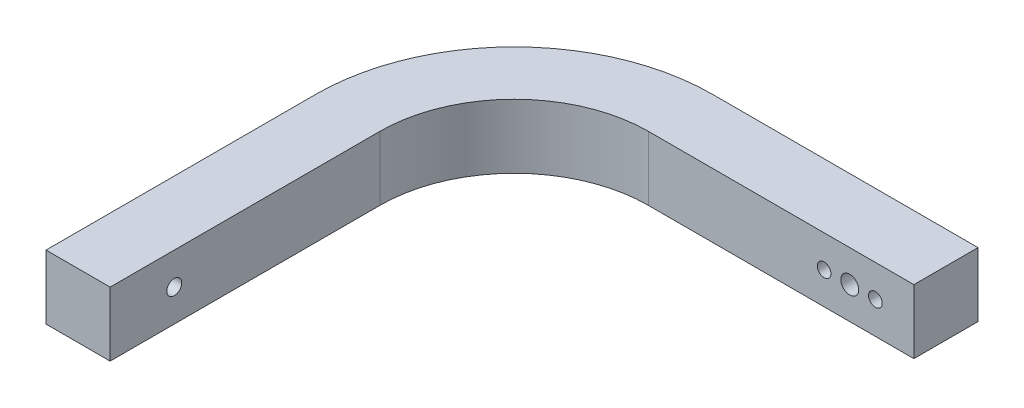
SolidWorks part; units mm, degrees
ref_plane "Front Plane" through (0, 0, 0) normal (0, 0, 1) x (1, 0, 0)
ref_plane "Top Plane" through (0, 0, 0) normal (0, 1, 0) x (1, 0, 0)
ref_plane "Right Plane" through (0, 0, 0) normal (1, 0, 0) x (0, 0, -1)
ref_axis "Z" through (0, 0, -5.375) along (0, 0, 1)
sketch "Sketch1" plane through (0, 0, 0) normal (0, 1, 0) x (1, 0, 0)
  line L0 (-47.1, 0) -> (47.1, 0) construction
  line L1 (-93.5, -46.4) -> (-93.5, -109.5)
  line L2 (-93.5, -109.5) -> (-78.5, -109.5)
  line L3 (-78.5, -109.5) -> (-78.5, -46.4)
  line L4 (-47.1, -15) -> (47.1, -15) construction
  line L5 (0, -15) -> (0, 0) construction
  line L6 (78.5, -109.5) -> (78.5, -46.4) construction
  line L7 (93.5, -109.5) -> (78.5, -109.5) construction
  line L8 (93.5, -46.4) -> (93.5, -109.5) construction
  line L9 (47.1, 0) -> (47.1, -15) construction
  line L10 (15, -15) -> (15, 0)
  line L11 (-47.1, -15) -> (15, -15)
  line L12 (-47.1, 0) -> (15, 0)
  line L13 (0, 5.375) -> (0, -112.875) construction
  arc A0 (-47.1, 0) -> (-93.5, -46.4) centre (-47.1, -46.4) ccw
  arc A1 (-78.5, -46.4) -> (-47.1, -15) centre (-47.1, -46.4) cw
  arc A2 (78.5, -46.4) -> (47.1, -15) centre (47.1, -46.4) ccw construction
  arc A3 (47.1, 0) -> (93.5, -46.4) centre (47.1, -46.4) cw construction
  point P10 (22.0594, -22.0981)
  dimension "D3" = 31.4
  dimension "D1" = 157
  dimension "D2" = 15
  dimension "D4" = 94.5
  dimension "D5" = 15
extrude "Boss-Extrude1" add sketch "Sketch1" along normal blind 7.5 and the other way blind 7.5
sketch "Sketch2" plane through (-78.5, 0, 0) normal (-1, 0, 0) x (0, 0, 1)
  line L1 (59.125, 0) -> (-59.125, 0) construction
  line L2 (0, -8.25) -> (0, 8.25) construction
  circle A0 centre (94.5, 0) radius 1.75
  dimension "D1" = 3.5
  dimension "D2" = 94.5
extrude "Cut-Extrude1" cut sketch "Sketch2" against normal through all both and the other way through all
ref_axis "Axis2" through (-120.1767, 0, 94.5) along (1, 0, 0)
sketch "Sketch3" plane through (0, 0, 0) normal (0, 0, -1) x (-1, 0, 0)
  line L0 (-6, 0) -> (6, 0) construction
  circle A0 centre (0, 0) radius 2.1
  circle A1 centre (-6, 0) radius 1.6
  circle A2 centre (6, 0) radius 1.6
  dimension "D1" = 4.2
  dimension "D3" = 3.2
  dimension "D2" = 12
extrude "Cut-Extrude2" cut sketch "Sketch3" against normal through all
sketch "Sketch4" plane through (-93.5, 0, 0) normal (1, 0, 0) x (0, 0, -1)
  circle A0 centre (-94.5, 0) radius 2.275
  circle A1 centre (-94.5, 0) radius 1.75 construction
  dimension "D1" = 4.55
extrude "Cut-Extrude3" cut sketch "Sketch4" along normal blind 6
sketch "Sketch5" plane through (-93.5, 0, 0) normal (-1, 0, 0) x (0, 0, 1)
  circle A0 centre (94.5, 0) radius 3.825
  dimension "D1" = 7.65
extrude "Cut-Extrude4" cut sketch "Sketch5" against normal blind 0.75
equation "\"width\"= \"EyeDiameter\" + \"EyeClearance\""
equation "\"prongwidth\"= \"L2Thickness\""
equation "\"D2@Sketch1\"=\"prongwidth\""
equation "\"D3@Sketch1\"=\"width\"/5"
equation "\"pronglength\"= \"BasePlaneDistance\"'model implicitly adds clearance (of prongwidth) to the hole drilled at the baseplanedistance"
equation "\"D4@Sketch1\"=\"pronglength\""
equation "\"D1@Boss-Extrude1\"=\"prongwidth\"/2"
equation "\"D2@Boss-Extrude1\"=\"prongwidth\"/2"
equation "\"lbracket-plane-to-axis\"= \"BasePlaneDistance\""
equation "\"D2@Sketch2\"=\"lbracket-plane-to-axis\""
equation "\"EyeDiameter\" = 155"
equation "\"BasePlaneDistance\" = \"EyeDiameter\"/2+\"L2Thickness\"+\"EyeClearance\""
equation "\"EyeClearance\" = 2"
equation "\"D1@Sketch1\"=\"EyeDiameter\"+\"EyeClearance\""
equation "\"BearingDepth\"= 6"
equation "\"BearingHousingID\"=4.5"
equation "\"D1@Sketch4\"=\"BearingHousingID\" + \"PrinterFilamentThickness\" * \"ApplyPrinterOffset\" / 2"
equation "\"D1@Cut-Extrude3\"=\"BearingDepth\""
equation "\"BearingFlangeThickness\"= 0.75"
equation "\"BearingFlangeOD\"=7.5"
equation "\"D1@Sketch5\"=\"BearingFlangeOD\" + \"PrinterFilamentThickness\"*1.5 *\"ApplyPrinterOffset\""
equation "\"D1@Cut-Extrude4\"=\"BearingFlangeThickness\""
equation "\"PrinterFilamentThickness\"= 0.1"
equation "\"ApplyPrinterOffset\"= 1'if 1, adjust hole sizes to try and make pressfits work with the 3d printer"
equation "\"L2Thickness\" = 15"
equation "\"L2_ID\" = 20"
equation "\"vx\" = 0"
equation "\"vy\" = 0"
equation "\"vz\" = 100"
equation "\"parametric_end\" = 1"
equation "\"Rw_3_xx\" = -(\"vz\")/sqr((\"vx\")^2 + (\"vz\")^2)"
equation "\"Rw_3_xy\" = 0"
equation "\"Rw_3_xz\" = (\"vx\")/sqr((\"vx\")^2 + (\"vz\")^2)"
equation "\"Rw_3_zx\" = (\"vx\")/sqr((\"vx\")^2 + (\"vy\")^2 + (\"vz\")^2)"
equation "\"Rw_3_zy\" = (\"vy\")/sqr((\"vx\")^2 + (\"vy\")^2 + (\"vz\")^2)"
equation "\"Rw_3_zz\" = (\"vz\")/sqr((\"vx\")^2 + (\"vy\")^2 + (\"vz\")^2)"
equation "\"Rw_3_yx\" = (\"vx\")*(\"vy\")/sqr((\"vx\")^4 + (\"vx\")^2*(\"vy\")^2 + 2*(\"vx\")^2*(\"vz\")^2 + (\"vy\")^2*(\"vz\")^2 + (\"vz\")^4)"
equation "\"Rw_3_yy\" = -sqr((\"vx\")^2 + (\"vz\")^2)/sqr((\"vx\")^2 + (\"vy\")^2 + (\"vz\")^2)"
equation "\"Rw_3_yz\" = (\"vy\")*(\"vz\")/sqr((\"vx\")^4 + (\"vx\")^2*(\"vy\")^2 + 2*(\"vx\")^2*(\"vz\")^2 + (\"vy\")^2*(\"vz\")^2 + (\"vz\")^4)"
equation "\"O2Targx\" = -\"BasePlaneDistance\"*(\"vx\")*(\"vy\")/sqr((\"vx\")^4 + (\"vx\")^2*(\"vy\")^2 + 2*(\"vx\")^2*(\"vz\")^2 + (\"vy\")^2*(\"vz\")^2 + (\"vz\")^4)"
equation "\"O2Targy\" = \"BasePlaneDistance\"*sqr((\"vx\")^2 + (\"vz\")^2)/sqr((\"vx\")^2 + (\"vy\")^2 + (\"vz\")^2)"
equation "\"O2Targz\" = -\"BasePlaneDistance\"*(\"vy\")*(\"vz\")/sqr((\"vx\")^4 + (\"vx\")^2*(\"vy\")^2 + 2*(\"vx\")^2*(\"vz\")^2 + (\"vy\")^2*(\"vz\")^2 + (\"vz\")^4)"
equation "\"O2Targx_0\" = -(\"BasePlaneDistance\")*sqr((\"vx\")^2 + (\"vz\")^2)/sqr((\"vx\")^2 + (\"vy\")^2 + (\"vz\")^2)"
equation "\"O2Targy_0\" = -(\"BasePlaneDistance\")*(\"vy\")*(\"vz\")/sqr((\"vx\")^4 + (\"vx\")^2*(\"vy\")^2 + 2*(\"vx\")^2*(\"vz\")^2 + (\"vy\")^2*(\"vz\")^2 + (\"vz\")^4)"
equation "\"O2Targz_0\" = (\"BasePlaneDistance\")*(\"vx\")*(\"vy\")/sqr((\"vx\")^4 + (\"vx\")^2*(\"vy\")^2 + 2*(\"vx\")^2*(\"vz\")^2 + (\"vy\")^2*(\"vz\")^2 + (\"vz\")^4) + (\"BasePlaneDistance\")"
equation "\"theta2_s1\" = arcsin(((\"BasePlaneDistance\") - (\"O2Targz_0\"))/(\"BasePlaneDistance\")) + pi"
equation "\"theta2_s2\" = -arcsin(((\"BasePlaneDistance\") - (\"O2Targz_0\"))/(\"BasePlaneDistance\"))"
equation "\"theta1_s1\" = arcsin((\"O2Targy_0\")/((\"BasePlaneDistance\")*cos((\"Theta2\")))) + pi"
equation "\"theta1_s2\" = -arcsin((\"O2Targy_0\")/((\"BasePlaneDistance\")*cos((\"Theta2\"))))"
equation "\"theta1_s3\" = -arccos(-(\"O2Targx_0\")/((\"BasePlaneDistance\")*cos((\"Theta2\")))) + 2*pi"
equation "\"theta1_s4\" = arccos(-(\"O2Targx_0\")/((\"BasePlaneDistance\")*cos((\"Theta2\"))))"
equation "\"Theta1\" = \"theta1_s2\" 'so far, theta1_s1 and theta1_s4 have agreed, and they agree with the sw constraint solver"
equation "\"Theta2\" = \"theta2_s2\""
equation "\"o2_x\" = -(\"BasePlaneDistance\")*cos((\"Theta1\"))*cos((\"Theta2\"))"
equation "\"o2_y\" = -(\"BasePlaneDistance\")*sin((\"Theta1\"))*cos((\"Theta2\"))"
equation "\"o2_z\" = (\"BasePlaneDistance\")*(sin((\"Theta2\")) + 1)"
equation "\"o1_x\" = (\"BasePlaneDistance\")*sin((\"Theta1\"))"
equation "\"o1_y\" = -(\"BasePlaneDistance\")*cos((\"Theta1\"))"
equation "\"o1_z\" = (\"BasePlaneDistance\")"
equation "\"Actuator1_Theta\" = atn(\"vx\"/\"vz\") 'ik solution for the single link joint"
equation "\"Actuator2_Theta\" = \"Theta1\"  'ik solution for the double link joint"
